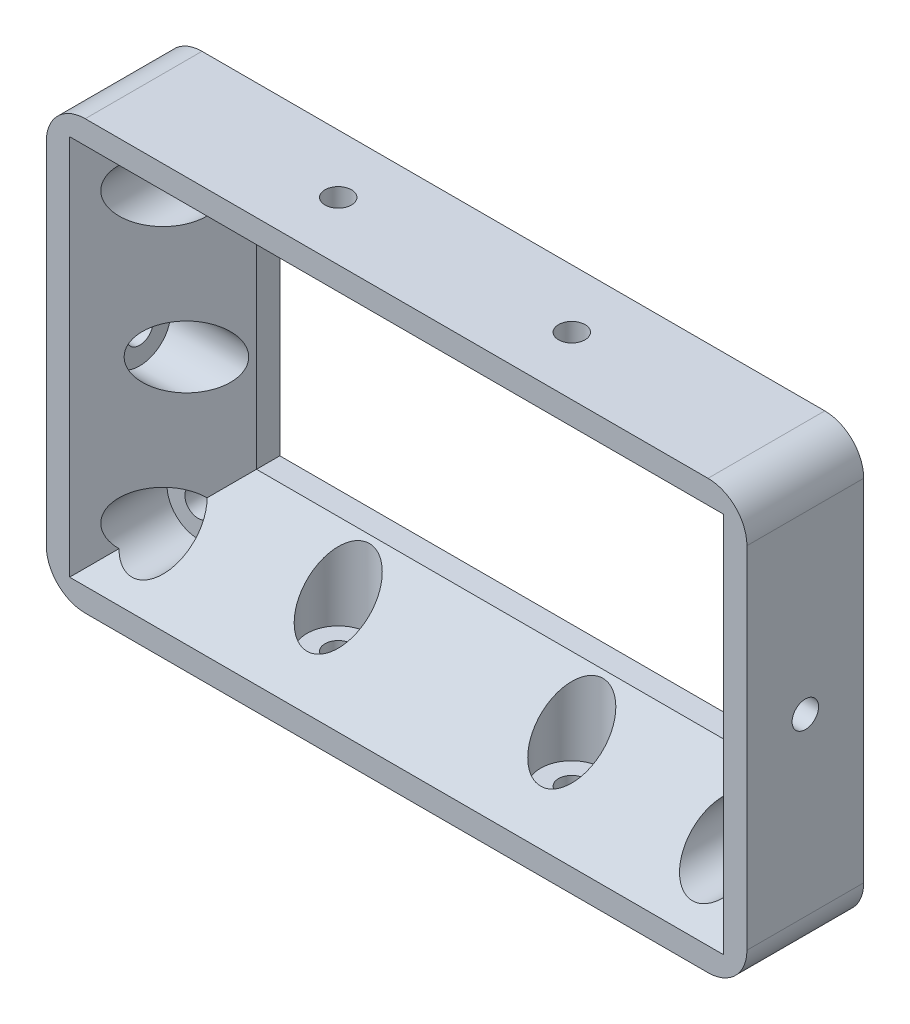
SolidWorks part; units mm, degrees
material "ABS"
ref_plane "Front Plane" through (0, 0, 0) normal (0, 0, 1) x (1, 0, 0)
ref_plane "Top Plane" through (0, 0, 0) normal (0, 1, 0) x (1, 0, 0)
ref_plane "Right Plane" through (0, 0, 0) normal (1, 0, 0) x (0, 0, -1)
sketch "Sketch1" plane through (0, 0, 0) normal (0, 0, 1) x (1, 0, 0)
  line L1 (-45, -27.5) -> (45, -27.5)
  line L2 (-45, -27.5) -> (-45, 27.5)
  line L3 (-45, 27.5) -> (45, 27.5)
  line L4 (45, -27.5) -> (45, 27.5)
  line L5 (-45, -27.5) -> (45, 27.5) construction
  line L6 (-45, 27.5) -> (45, -27.5) construction
  point P0 (0, 0)
extrude "Boss-Extrude1" add sketch "Sketch1" along normal blind 15
sketch "Sketch2" plane through (0, 0, 15) normal (0, 0, 1) x (1, 0, 0)
  line L0 (45, 27.5) -> (-45, 27.5) construction
  line L1 (-30, -12.5) -> (30, -12.5)
  line L2 (-30, -12.5) -> (-30, 12.5)
  line L3 (-30, 12.5) -> (30, 12.5)
  line L4 (30, -12.5) -> (30, 12.5)
  line L5 (-45, -27.5) -> (45, -27.5) construction
  line L6 (-45, 27.5) -> (-45, -27.5) construction
  line L7 (45, -27.5) -> (45, 27.5) construction
  dimension "D1" = 15
  dimension "D2" = 15
  dimension "D3" = 15
  dimension "D4" = 15
extrude "Cut-Extrude1" cut sketch "Sketch2" against normal through all
hole_wizard "CBORE for M3 SBHCS1" positions "Sketch4" profile "Sketch3" counterbore size "M3" standard "ANSI Metric" end condition through all
sketch "Sketch4" plane through (0, 0, 15) normal (0, 0, 1) x (1, 0, 0)
  line L0 (45, 27.5) -> (-45, 27.5) construction
  line L1 (-45, 27.5) -> (-45, -27.5) construction
  point P0 (-36, -18.5)
  point P2 (-36, 18.5)
  point P4 (36, 18.5)
  point P6 (36, -18.5)
  dimension "D1" = 72
  dimension "D2" = 37
  dimension "D3" = 37
  dimension "D4" = 9
  dimension "D5" = 72
  dimension "D6" = 9
  dimension "D7" = 9
sketch "Sketch3" plane through (-36, -18.5, 15) normal (1, 0, 0) x (0, -1, 0)
  line L0 (0, 0) -> (0, 15)
  line L1 (0, 15) -> (1.7, 15)
  line L3 (1.7, 15) -> (1.7, 10.5)
  line L4 (1.7, 10.5) -> (4, 10.5)
  line L5 (4, 10.5) -> (4, 0)
  line L7 (4, 0) -> (0, 0)
  line L11 (0, -6.35) -> (0, 107.95) construction
  dimension "Thru Hole Dia." = 3.4
  dimension "Thru Hole Depth" = 15
  dimension "C'Bore Dia." = 8
  dimension "C'Bore Depth" = 10.5
fillet "Fillet7" radius 5 1 edges at (-45, -27.5, 7.5) type face fillet first side face at (-45, 0, 7.5) second side face at (0, -27.5, 7.5)
fillet "Fillet8" radius 5 1 edges at (-45, 27.5, 7.5) type face fillet first side face at (0, 27.5, 7.5) second side face at (-45, 2.5, 7.5)
fillet "Fillet9" radius 5 1 edges at (45, 27.5, 7.5) type face fillet first side face at (2.5, 27.5, 7.5) second side face at (45, 0, 7.5)
fillet "Fillet10" radius 5 1 edges at (45, -27.5, 7.5) type face fillet first side face at (2.5, -27.5, 7.5) second side face at (45, -2.5, 7.5)
hole_wizard "CBORE for M3 SBHCS2" positions "Sketch6" profile "Sketch5" counterbore size "M3" standard "ANSI Metric" end condition through all
sketch "Sketch6" plane through (-30, 0, 0) normal (1, 0, 0) x (0, 0, -1)
  line L0 (-15, 12.5) -> (-15, -12.5) construction
  line L1 (0, -12.5) -> (-15, -12.5) construction
  point P0 (-7.5, 0)
  dimension "D1" = 7.5
  dimension "D2" = 12.5
sketch "Sketch5" plane through (-30, 0, 7.5) normal (0, 1, 0) x (0, 0, -1)
  line L0 (0, 0) -> (0, 15)
  line L1 (0, 15) -> (1.7, 15)
  line L3 (1.7, 15) -> (1.7, 10.5)
  line L4 (1.7, 10.5) -> (4, 10.5)
  line L5 (4, 10.5) -> (4, 0)
  line L7 (4, 0) -> (0, 0)
  line L11 (0, -6.35) -> (0, 107.95) construction
  dimension "Thru Hole Dia." = 3.4
  dimension "Thru Hole Depth" = 15
  dimension "C'Bore Dia." = 8
  dimension "C'Bore Depth" = 10.5
hole_wizard "CBORE for M3 SBHCS6" positions "Sketch14" profile "Sketch13" counterbore size "M3" standard "ANSI Metric" end condition through all
sketch "Sketch14" plane through (0, -12.5, 0) normal (0, 1, 0) x (1, 0, 0)
  line L0 (-30, -15) -> (30, -15) construction
  line L1 (30, 0) -> (30, -15) construction
  line L2 (-30, 0) -> (-30, -15) construction
  point P0 (-15, -7.5)
  point P2 (15, -7.5)
  dimension "D1" = 7.5
  dimension "D2" = 7.5
  dimension "D3" = 15
  dimension "D4" = 15
sketch "Sketch13" plane through (-15, -12.5, 7.5) normal (1, 0, 0) x (0, 0, 1)
  line L0 (0, 0) -> (0, 15)
  line L1 (0, 15) -> (1.7, 15)
  line L3 (1.7, 15) -> (1.7, 10.5)
  line L4 (1.7, 10.5) -> (4, 10.5)
  line L5 (4, 10.5) -> (4, 0)
  line L7 (4, 0) -> (0, 0)
  line L11 (0, -6.35) -> (0, 107.95) construction
  dimension "Thru Hole Dia." = 3.4
  dimension "Thru Hole Depth" = 15
  dimension "C'Bore Dia." = 8
  dimension "C'Bore Depth" = 10.5
hole_wizard "CBORE for M3 SBHCS7" positions "Sketch16" profile "Sketch15" counterbore size "M3" standard "ANSI Metric" end condition through all
sketch "Sketch16" plane through (0, 12.5, 0) normal (0, -1, 0) x (-1, 0, 0)
  line L0 (-30, 0) -> (-30, -15) construction
  line L1 (30, 0) -> (30, -15) construction
  line L2 (-30, 0) -> (30, 0) construction
  point P0 (15, -7.5)
  point P2 (-15, -7.5)
  point P7 (30, -7.5)
  dimension "D1" = 15
  dimension "D2" = 15
  dimension "D3" = 7.5
  dimension "D4" = 7.5
sketch "Sketch15" plane through (-15, 12.5, 7.5) normal (1, 0, 0) x (0, 0, -1)
  line L0 (0, 0) -> (0, 15)
  line L1 (0, 15) -> (1.7, 15)
  line L3 (1.7, 15) -> (1.7, 10.5)
  line L4 (1.7, 10.5) -> (4, 10.5)
  line L5 (4, 10.5) -> (4, 0)
  line L7 (4, 0) -> (0, 0)
  line L11 (0, -6.35) -> (0, 107.95) construction
  dimension "Thru Hole Dia." = 3.4
  dimension "Thru Hole Depth" = 15
  dimension "C'Bore Dia." = 8
  dimension "C'Bore Depth" = 10.5
hole_wizard "CBORE for M3 SBHCS8" positions "Sketch18" profile "Sketch17" counterbore size "M3" standard "ANSI Metric" end condition through all
sketch "Sketch18" plane through (30, 0, 0) normal (-1, 0, 0) x (0, 0, 1)
  line L0 (15, -12.5) -> (15, 12.5) construction
  line L1 (0, 12.5) -> (15, 12.5) construction
  point P0 (7.5, 0)
  dimension "D1" = 7.5
  dimension "D2" = 12.5
sketch "Sketch17" plane through (30, 0, 7.5) normal (0, 1, 0) x (0, 0, 1)
  line L0 (0, 0) -> (0, 15)
  line L1 (0, 15) -> (1.7, 15)
  line L3 (1.7, 15) -> (1.7, 10.5)
  line L4 (1.7, 10.5) -> (4, 10.5)
  line L5 (4, 10.5) -> (4, 0)
  line L7 (4, 0) -> (0, 0)
  line L11 (0, -6.35) -> (0, 107.95) construction
  dimension "Thru Hole Dia." = 3.4
  dimension "Thru Hole Depth" = 15
  dimension "C'Bore Dia." = 8
  dimension "C'Bore Depth" = 10.5
chamfer "Chamfer5" distance 12 angle 45 1 edges at (0, 12.5, 15)
chamfer "Chamfer7" distance 12 angle 45 1 edges at (0, -12.5, 15)
chamfer "Chamfer8" distance 12 angle 45 1 edges at (30, 0, 15)
chamfer "Chamfer9" distance 12 angle 45 1 edges at (-30, 0, 15)
